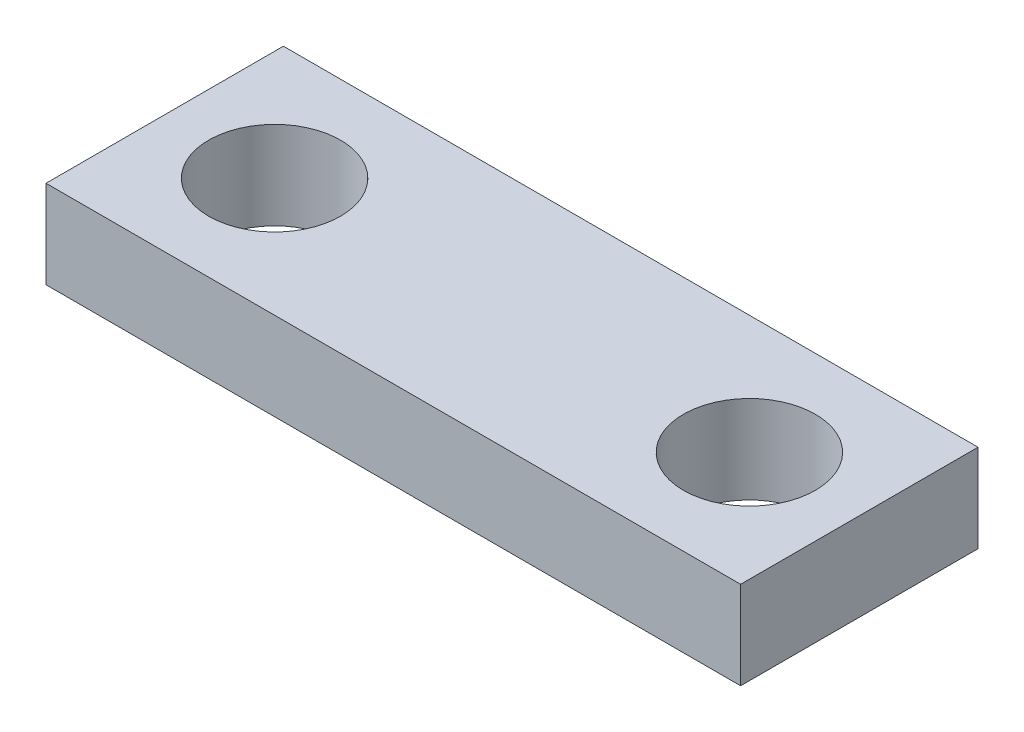
SolidWorks part; units mm, degrees
ref_plane "前视基准面" through (0, 0, 0) normal (0, 0, 1) x (1, 0, 0)
ref_plane "上视基准面" through (0, 0, 0) normal (0, 1, 0) x (1, 0, 0)
ref_plane "右视基准面" through (0, 0, 0) normal (1, 0, 0) x (0, 0, -1)
sketch "草图1" plane through (0, 0, 0) normal (0, 1, 0) x (1, 0, 0)
  line L1 (-39.5, 13.5) -> (39.5, 13.5)
  line L2 (-39.5, 13.5) -> (-39.5, -13.5)
  line L3 (-39.5, -13.5) -> (39.5, -13.5)
  line L4 (39.5, 13.5) -> (39.5, -13.5)
  line L5 (-39.5, 13.5) -> (39.5, -13.5) construction
  line L6 (-39.5, -13.5) -> (39.5, 13.5) construction
  point P0 (0, 0)
  dimension "D1" = 79
  dimension "D2" = 27
extrude "凸台-拉伸1" add sketch "草图1" along normal blind 10
sketch "草图2" plane through (0, 0, 0) normal (0, -1, 0) x (1, 0, 0)
  line L0 (-39.5, 0) -> (39.5, 0) construction
  line L1 (-39.5, -13.5) -> (-39.5, 13.5) construction
  line L2 (39.5, 13.5) -> (39.5, -13.5) construction
ref_plane "基准面1" through (0, 0, 0) normal (0, 0, 1) x (1, 0, 0)
sketch "草图3" plane through (0, 10, 0) normal (0, 1, 0) x (1, 0, 0)
  line L0 (-14.85, 0) -> (14.85, 0) construction
  line L1 (0, 13.5) -> (0, -13.5) construction
  line L2 (39.5, 13.5) -> (-39.5, 13.5) construction
  line L3 (-39.5, -13.5) -> (39.5, -13.5) construction
  circle A0 centre (-27, 0) radius 7.5
  circle A1 centre (27, 0) radius 7.5
  dimension "D1" = 15
  dimension "D2" = 54
extrude "切除-拉伸1" cut sketch "草图3" against normal through all contours A1 | A0
